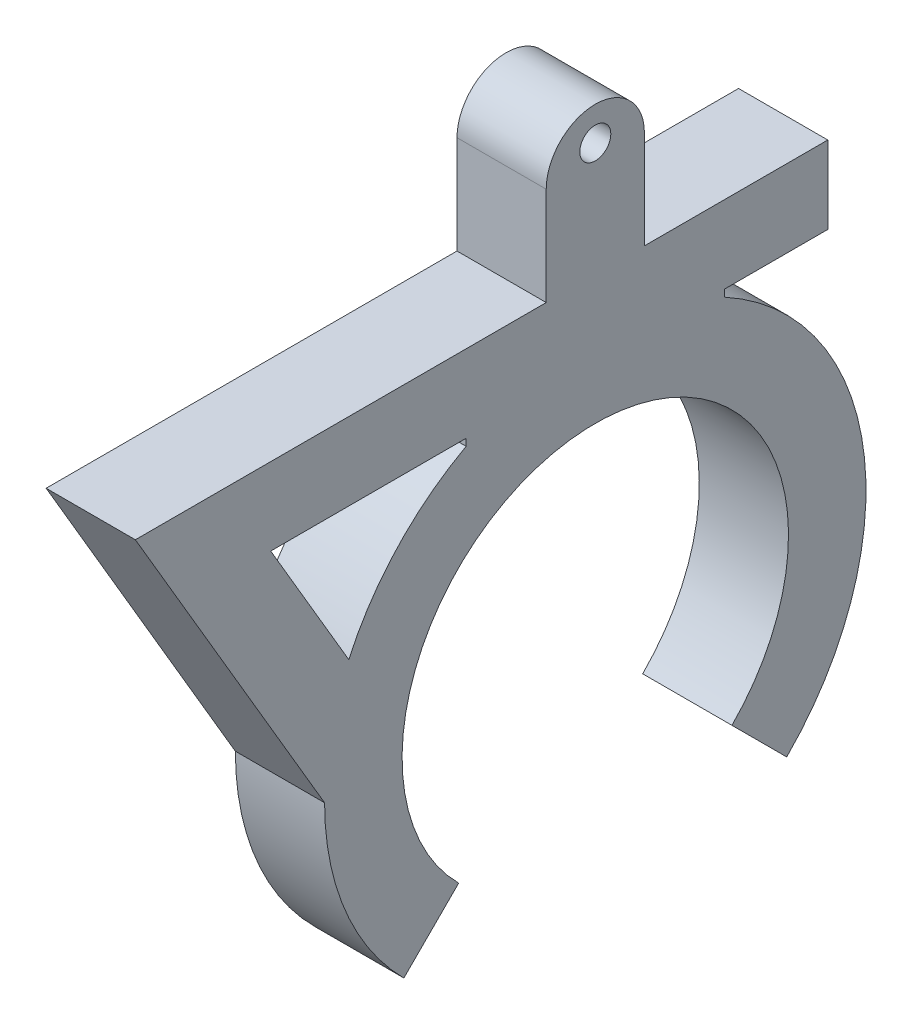
SolidWorks part; units mm, degrees
ref_plane "Front Plane" through (0, 0, 0) normal (0, 0, 1) x (1, 0, 0)
ref_plane "Top Plane" through (0, 0, 0) normal (0, 1, 0) x (1, 0, 0)
ref_plane "Right Plane" through (0, 0, 0) normal (1, 0, 0) x (0, 0, -1)
sketch "Sketch1" plane through (0, 0, 0) normal (1, 0, 0) x (0, 0, -1)
  line L0 (-2.6446, -2.6446) -> (2.6446, -2.6446) construction
  line L1 (-2.6446, -2.6446) -> (-3.7052, -3.7052)
  line L2 (3.7052, -3.7052) -> (2.6446, -2.6446)
  line L3 (0, 0) -> (0, 6.3411) construction
  line L4 (-2.5, 6.24) -> (-0.95, 6.24)
  line L5 (-2.5, 6.24) -> (-2.5, 4.6052)
  line L6 (-0.95, 8.14) -> (-0.95, 6.24)
  line L7 (2.5, 6.24) -> (2.5, 4.6052)
  line L8 (-2.5, 6.24) -> (2.5, 4.6052) construction
  line L9 (-2.5, 4.6052) -> (2.5, 6.24) construction
  line L10 (-0.95, 8.14) -> (0.95, 8.14) construction
  line L11 (0.95, 6.24) -> (2.5, 6.24)
  line L12 (0.95, 8.14) -> (0.95, 6.24)
  line L13 (-0.95, 8.14) -> (0.95, 6.24) construction
  line L14 (-0.95, 6.24) -> (0.95, 8.14) construction
  line L15 (-2.5, 6.24) -> (-8.9027, 6.24)
  line L16 (-8.9027, 6.24) -> (-5.24, 0)
  line L17 (-2.5, 4.74) -> (-6.2829, 4.74)
  line L18 (-6.2829, 4.74) -> (-4.7717, 2.1653)
  line L19 (-6.2829, 4.74) -> (-3.9464, 0.7593) construction
  line L21 (2.5, 6.24) -> (4.5, 6.24)
  line L22 (2.5, 6.24) -> (2.5, 4.74)
  line L23 (2.5, 4.74) -> (4.5, 4.74)
  line L24 (4.5, 6.24) -> (4.5, 4.74)
  arc A0 (-2.6446, -2.6446) -> (2.6446, -2.6446) centre (0, 0) cw
  arc A1 (-3.7052, -3.7052) -> (-2.5, 4.6052) centre (0, 0) cw
  arc A2 (2.5, 4.6052) -> (3.7052, -3.7052) centre (0, 0) cw
  arc A3 (-3.7052, -3.7052) -> (3.7052, -3.7052) centre (0, 0) cw construction
  arc A4 (-0.95, 8.14) -> (0.95, 8.14) centre (0, 8.14) cw
  circle A5 centre (0, 8.44) radius 0.3
  point P7 (0, 5.4226)
  point P12 (0, 3.74)
  point P16 (0, 8.14)
  point P17 (0, 7.19)
  dimension "D1" = 3.74
  dimension "D3" = 1.5
  dimension "D6" = 1.9
  dimension "D8" = 0.6
  dimension "D9" = 1.5
  dimension "D2" = 90
  dimension "D4" = 2.5
  dimension "D5" = 5
  dimension "D7" = 1.9
  dimension "D10" = 2
extrude "Boss-Extrude1" add sketch "Sketch1" along normal blind 1.7272 contours A4 L6 L4 L5 A1 L1 A0 L2 A2 L7 L11 L12 A5 | L16 A1 L18 L17 L5 L15 | L24 L21 L7 L23 region at (0, -3.058, 3.2919) region at (0, 3.1653, 6.9942) region at (0, 5.49, -3.5)
